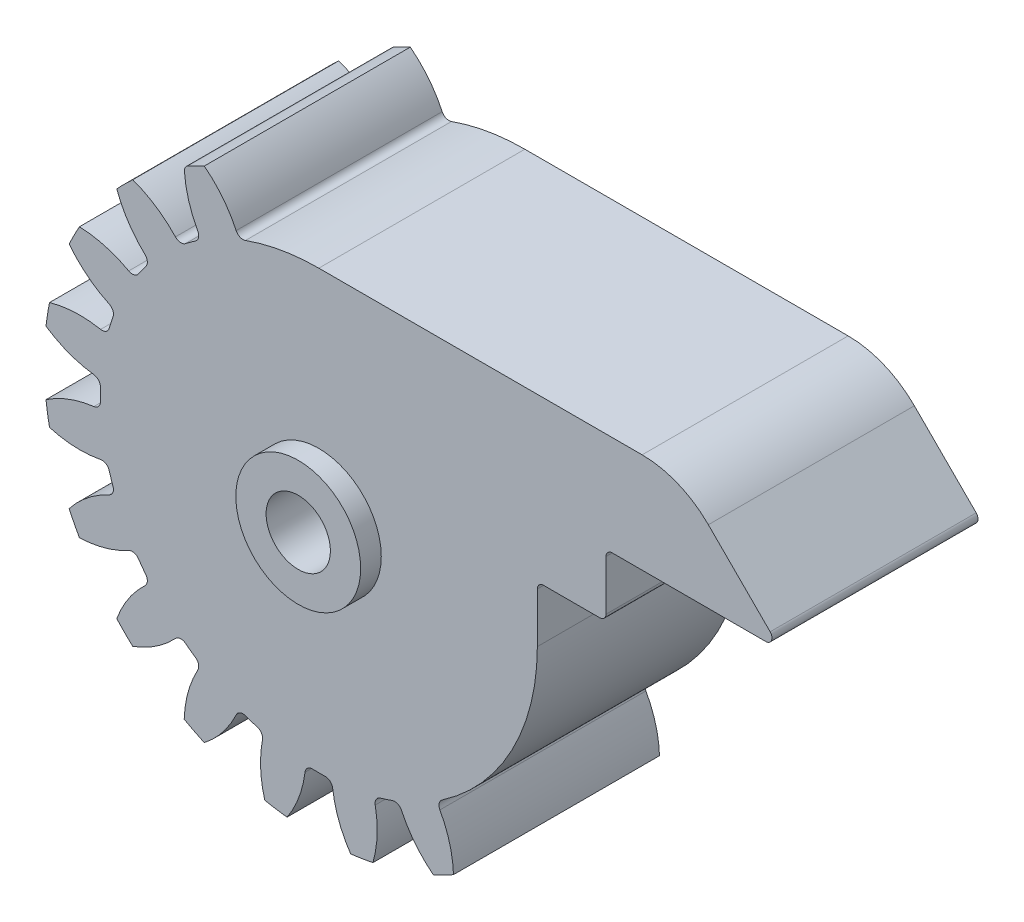
SolidWorks part; units mm, degrees
material "1023 Carbon Steel Sheet (SS)"
ref_plane "Front Plane" through (0, 0, 0) normal (0, 0, 1) x (1, 0, 0)
ref_plane "Top Plane" through (0, 0, 0) normal (0, 1, 0) x (1, 0, 0)
ref_plane "Right Plane" through (0, 0, 0) normal (1, 0, 0) x (0, 0, -1)
sketch "skBase" plane through (0, 0, 0) normal (0, 0, 1) x (1, 0, 0)
  circle A0 centre (0, 0) radius 20
  circle A1 centre (0, 0) radius 22
  circle A2 centre (0, 0) radius 17.5
  dimension "D1" = 40
  dimension "D3" = 4.5
extrude "Base" add sketch "skBase" along normal mid plane 16.5 contours A1
sketch "skToothProfile" plane through (0, 0, 0) normal (0, 0, 1) x (1, 0, 0)
  line L0 (0, 0) -> (0, 22) construction
  line L1 (-1.5692, 19.9383) -> (1.5692, 19.9383) construction
  line L2 (-1.0563, 17.4681) -> (0, 0) construction
  line L3 (0, 15.6271) -> (-2.6287, 22.8493) construction
  line L4 (0, 0) -> (3.4416, 21.7291) construction
  line L5 (1.5692, 19.9383) -> (4.6689, 19.4474) construction
  circle A0 centre (0, 0) radius 22 construction
  arc A1 (-1.0563, 17.4681) -> (-3.258, 22.7681) centre (-9.8105, 16.9387) ccw
  arc A2 (1.0563, 17.4681) -> (3.258, 22.7681) centre (9.8105, 16.9387) cw
  circle A3 centre (0, 0) radius 17.5 construction
  arc A4 (1.0563, 17.4681) -> (-1.0563, 17.4681) centre (0, 0) ccw
  circle A5 centre (0, 0) radius 20 construction
  circle A6 centre (0, 0) radius 22 construction
  circle A7 centre (0, 0) radius 23
  arc A8 (3.258, 22.7681) -> (-3.258, 22.7681) centre (0, 0) ccw
  dimension "D2" = 20
  dimension "D3" = 9
extrude "ToothProfile" cut sketch "skToothProfile" against normal through all and the other way through all
fillet "FilletToothProfile" radius 0.6 2 edges at (1.0563, 17.4681, 0) (-1.0563, 17.4681, 0)
pattern_circular "CirPatternTeeth" count 20 over 360 about axis through (0, 0, 8.25) along (0, 0, 1) of "ToothProfile", "FilletToothProfile"
sketch "skChaveta" plane through (0, 0, 8.25) normal (0, 0, 1) x (1, 0, 0)
  line L0 (0, 2.575) -> (0, 0) construction
  circle A0 centre (0, 0) radius 2.575
  dimension "D1" = 5.15
extrude "Chaveta" cut sketch "skChaveta" against normal through all contours A0
sketch "skRebaixo" plane through (0, 0, 8.25) normal (0, 0, 1) x (1, 0, 0)
  circle A0 centre (0, 0) radius 21.5
  circle A1 centre (0, 0) radius 7.5
  dimension "D1" = 43
  dimension "D2" = 15
sketch "Sketch4" plane through (0, 0, -8.25) normal (0, 0, -1) x (-1, 0, 0)
  circle A0 centre (0, 0) radius 17.5
  arc A5 (-2.5459, 21.8522) -> (-4.3314, 21.5694) centre (0, 0) ccw
  arc A6 (-2.5459, 21.8522) -> (-4.3314, 21.5694) centre (0, 0) ccw
  arc A7 (-18.0189, -1.107) -> (-21.8522, -2.5459) centre (-16.9387, -9.8105) ccw
  arc A8 (-18.0189, -1.107) -> (-21.8522, -2.5459) centre (-16.9387, -9.8105) ccw
  arc A9 (-21.5694, -4.3314) -> (-17.4791, -4.5153) centre (-19.1413, 4.096) ccw
  arc A10 (-21.5694, -4.3314) -> (-17.4791, -4.5153) centre (-19.1413, 4.096) ccw
  arc A127 (-19.996, -9.174) -> (-19.1752, -10.7848) centre (0, 0) ccw
  arc A128 (-19.996, -9.174) -> (-19.1752, -10.7848) centre (0, 0) ccw
  arc A129 (-16.1824, -14.904) -> (-14.904, -16.1824) centre (0, 0) ccw
  arc A130 (-16.1824, -14.904) -> (-14.904, -16.1824) centre (0, 0) ccw
  arc A131 (-10.7848, -19.1752) -> (-9.174, -19.996) centre (0, 0) ccw
  arc A132 (-10.7848, -19.1752) -> (-9.174, -19.996) centre (0, 0) ccw
  arc A133 (-4.3314, -21.5694) -> (-2.5459, -21.8522) centre (0, 0) ccw
  arc A134 (-4.3314, -21.5694) -> (-2.5459, -21.8522) centre (0, 0) ccw
  arc A135 (2.5459, -21.8522) -> (4.3314, -21.5694) centre (0, 0) ccw
  arc A136 (2.5459, -21.8522) -> (4.3314, -21.5694) centre (0, 0) ccw
  arc A137 (9.174, -19.996) -> (10.7848, -19.1752) centre (0, 0) ccw
  arc A138 (9.174, -19.996) -> (10.7848, -19.1752) centre (0, 0) ccw
  arc A139 (14.904, -16.1824) -> (16.1824, -14.904) centre (0, 0) ccw
  arc A140 (14.904, -16.1824) -> (16.1824, -14.904) centre (0, 0) ccw
  arc A141 (19.1752, -10.7848) -> (19.996, -9.174) centre (0, 0) ccw
  arc A142 (19.1752, -10.7848) -> (19.996, -9.174) centre (0, 0) ccw
  arc A143 (21.5694, -4.3314) -> (21.8522, -2.5459) centre (0, 0) ccw
  arc A144 (21.5694, -4.3314) -> (21.8522, -2.5459) centre (0, 0) ccw
  arc A145 (21.8522, 2.5459) -> (21.5694, 4.3314) centre (0, 0) ccw
  arc A146 (21.8522, 2.5459) -> (21.5694, 4.3314) centre (0, 0) ccw
  arc A147 (19.996, 9.174) -> (19.1752, 10.7848) centre (0, 0) ccw
  arc A148 (19.996, 9.174) -> (19.1752, 10.7848) centre (0, 0) ccw
  arc A149 (16.1824, 14.904) -> (14.904, 16.1824) centre (0, 0) ccw
  arc A150 (16.1824, 14.904) -> (14.904, 16.1824) centre (0, 0) ccw
  arc A151 (10.7848, 19.1752) -> (9.174, 19.996) centre (0, 0) ccw
  arc A152 (10.7848, 19.1752) -> (9.174, 19.996) centre (0, 0) ccw
  arc A153 (4.3314, 21.5694) -> (2.5459, 21.8522) centre (0, 0) ccw
  arc A154 (4.3314, 21.5694) -> (2.5459, 21.8522) centre (0, 0) ccw
  arc A155 (-9.174, 19.996) -> (-10.7848, 19.1752) centre (0, 0) ccw
  arc A156 (-9.174, 19.996) -> (-10.7848, 19.1752) centre (0, 0) ccw
  arc A157 (-14.904, 16.1824) -> (-16.1824, 14.904) centre (0, 0) ccw
  arc A158 (-14.904, 16.1824) -> (-16.1824, 14.904) centre (0, 0) ccw
  arc A159 (-19.1752, 10.7848) -> (-19.996, 9.174) centre (0, 0) ccw
  arc A160 (-19.1752, 10.7848) -> (-19.996, 9.174) centre (0, 0) ccw
  arc A161 (-21.5694, 4.3314) -> (-21.8522, 2.5459) centre (0, 0) ccw
  arc A162 (-21.5694, 4.3314) -> (-21.8522, 2.5459) centre (0, 0) ccw
  arc A163 (-4.3314, 21.5694) -> (-4.5153, 17.4791) centre (4.096, 19.1413) ccw
  arc A164 (-4.3314, 21.5694) -> (-4.5153, 17.4791) centre (4.096, 19.1413) ccw
  arc A165 (-4.9352, 16.7897) -> (-4.5153, 17.4791) centre (-5.1044, 17.3653) ccw
  arc A166 (-4.9352, 16.7897) -> (-4.5153, 17.4791) centre (-5.1044, 17.3653) ccw
  arc A167 (-4.9352, 16.7897) -> (-5.8761, 16.484) centre (0, 0) ccw
  arc A168 (-4.9352, 16.7897) -> (-5.8761, 16.484) centre (0, 0) ccw
  arc A169 (-6.621, 16.7949) -> (-5.8761, 16.484) centre (-6.0775, 17.0492) ccw
  arc A170 (-6.621, 16.7949) -> (-5.8761, 16.484) centre (-6.0775, 17.0492) ccw
  arc A171 (-6.621, 16.7949) -> (-9.174, 19.996) centre (-14.5647, 13.0781) ccw
  arc A172 (-6.621, 16.7949) -> (-9.174, 19.996) centre (-14.5647, 13.0781) ccw
  arc A173 (-10.7848, 19.1752) -> (-9.6956, 15.2283) centre (-2.0195, 19.4702) ccw
  arc A174 (-10.7848, 19.1752) -> (-9.6956, 15.2283) centre (-2.0195, 19.4702) ccw
  arc A175 (-9.882, 14.4429) -> (-9.6956, 15.2283) centre (-10.2208, 14.9381) ccw
  arc A176 (-9.882, 14.4429) -> (-9.6956, 15.2283) centre (-10.2208, 14.9381) ccw
  arc A177 (-9.882, 14.4429) -> (-10.6823, 13.8614) centre (0, 0) ccw
  arc A178 (-9.882, 14.4429) -> (-10.6823, 13.8614) centre (0, 0) ccw
  arc A179 (-11.4868, 13.9269) -> (-10.6823, 13.8614) centre (-11.0486, 14.3366) ccw
  arc A180 (-11.4868, 13.9269) -> (-10.6823, 13.8614) centre (-11.0486, 14.3366) ccw
  arc A181 (-11.4868, 13.9269) -> (-14.904, 16.1824) centre (-17.8932, 7.9372) ccw
  arc A182 (-11.4868, 13.9269) -> (-14.904, 16.1824) centre (-17.8932, 7.9372) ccw
  arc A183 (-16.1824, 14.904) -> (-13.9269, 11.4868) centre (-7.9372, 17.8932) ccw
  arc A184 (-16.1824, 14.904) -> (-13.9269, 11.4868) centre (-7.9372, 17.8932) ccw
  arc A185 (-13.8614, 10.6823) -> (-13.9269, 11.4868) centre (-14.3366, 11.0486) ccw
  arc A186 (-13.8614, 10.6823) -> (-13.9269, 11.4868) centre (-14.3366, 11.0486) ccw
  arc A187 (-13.8614, 10.6823) -> (-14.4429, 9.882) centre (0, 0) ccw
  arc A188 (-13.8614, 10.6823) -> (-14.4429, 9.882) centre (0, 0) ccw
  arc A189 (-15.2283, 9.6956) -> (-14.4429, 9.882) centre (-14.9381, 10.2208) ccw
  arc A190 (-15.2283, 9.6956) -> (-14.4429, 9.882) centre (-14.9381, 10.2208) ccw
  arc A191 (-15.2283, 9.6956) -> (-19.1752, 10.7848) centre (-19.4702, 2.0195) ccw
  arc A192 (-15.2283, 9.6956) -> (-19.1752, 10.7848) centre (-19.4702, 2.0195) ccw
  arc A193 (-19.996, 9.174) -> (-16.7949, 6.621) centre (-13.0781, 14.5647) ccw
  arc A194 (-19.996, 9.174) -> (-16.7949, 6.621) centre (-13.0781, 14.5647) ccw
  arc A195 (-16.484, 5.8761) -> (-16.7949, 6.621) centre (-17.0492, 6.0775) ccw
  arc A196 (-16.484, 5.8761) -> (-16.7949, 6.621) centre (-17.0492, 6.0775) ccw
  arc A197 (-16.484, 5.8761) -> (-16.7897, 4.9352) centre (0, 0) ccw
  arc A198 (-16.484, 5.8761) -> (-16.7897, 4.9352) centre (0, 0) ccw
  arc A199 (-17.4791, 4.5153) -> (-16.7897, 4.9352) centre (-17.3653, 5.1044) ccw
  arc A200 (-17.4791, 4.5153) -> (-16.7897, 4.9352) centre (-17.3653, 5.1044) ccw
  arc A201 (-17.4791, 4.5153) -> (-21.5694, 4.3314) centre (-19.1413, -4.096) ccw
  arc A202 (-17.4791, 4.5153) -> (-21.5694, 4.3314) centre (-19.1413, -4.096) ccw
  arc A203 (-21.8522, 2.5459) -> (-18.0189, 1.107) centre (-16.9387, 9.8105) ccw
  arc A204 (-21.8522, 2.5459) -> (-18.0189, 1.107) centre (-16.9387, 9.8105) ccw
  arc A205 (-17.493, 0.4946) -> (-18.0189, 1.107) centre (-18.0928, 0.5116) ccw
  arc A206 (-17.493, 0.4946) -> (-18.0189, 1.107) centre (-18.0928, 0.5116) ccw
  arc A207 (-17.493, 0.4946) -> (-17.493, -0.4946) centre (0, 0) ccw
  arc A208 (-17.493, 0.4946) -> (-17.493, -0.4946) centre (0, 0) ccw
  arc A209 (-18.0189, -1.107) -> (-17.493, -0.4946) centre (-18.0928, -0.5116) ccw
  arc A210 (-18.0189, -1.107) -> (-17.493, -0.4946) centre (-18.0928, -0.5116) ccw
  arc A211 (-16.7897, -4.9352) -> (-17.4791, -4.5153) centre (-17.3653, -5.1044) ccw
  arc A212 (-16.7897, -4.9352) -> (-17.4791, -4.5153) centre (-17.3653, -5.1044) ccw
  arc A213 (-16.7897, -4.9352) -> (-16.484, -5.8761) centre (0, 0) ccw
  arc A214 (-16.7897, -4.9352) -> (-16.484, -5.8761) centre (0, 0) ccw
  arc A215 (-16.7949, -6.621) -> (-16.484, -5.8761) centre (-17.0492, -6.0775) ccw
  arc A216 (-16.7949, -6.621) -> (-16.484, -5.8761) centre (-17.0492, -6.0775) ccw
  arc A217 (-16.7949, -6.621) -> (-19.996, -9.174) centre (-13.0781, -14.5647) ccw
  arc A218 (-16.7949, -6.621) -> (-19.996, -9.174) centre (-13.0781, -14.5647) ccw
  arc A219 (-19.1752, -10.7848) -> (-15.2283, -9.6956) centre (-19.4702, -2.0195) ccw
  arc A220 (-19.1752, -10.7848) -> (-15.2283, -9.6956) centre (-19.4702, -2.0195) ccw
  arc A221 (-14.4429, -9.882) -> (-15.2283, -9.6956) centre (-14.9381, -10.2208) ccw
  arc A222 (-14.4429, -9.882) -> (-15.2283, -9.6956) centre (-14.9381, -10.2208) ccw
  arc A223 (-14.4429, -9.882) -> (-13.8614, -10.6823) centre (0, 0) ccw
  arc A224 (-14.4429, -9.882) -> (-13.8614, -10.6823) centre (0, 0) ccw
  arc A225 (-13.9269, -11.4868) -> (-13.8614, -10.6823) centre (-14.3366, -11.0486) ccw
  arc A226 (-13.9269, -11.4868) -> (-13.8614, -10.6823) centre (-14.3366, -11.0486) ccw
  arc A227 (-13.9269, -11.4868) -> (-16.1824, -14.904) centre (-7.9372, -17.8932) ccw
  arc A228 (-13.9269, -11.4868) -> (-16.1824, -14.904) centre (-7.9372, -17.8932) ccw
  arc A229 (-14.904, -16.1824) -> (-11.4868, -13.9269) centre (-17.8932, -7.9372) ccw
  arc A230 (-14.904, -16.1824) -> (-11.4868, -13.9269) centre (-17.8932, -7.9372) ccw
  arc A231 (-10.6823, -13.8614) -> (-11.4868, -13.9269) centre (-11.0486, -14.3366) ccw
  arc A232 (-10.6823, -13.8614) -> (-11.4868, -13.9269) centre (-11.0486, -14.3366) ccw
  arc A233 (-10.6823, -13.8614) -> (-9.882, -14.4429) centre (0, 0) ccw
  arc A234 (-10.6823, -13.8614) -> (-9.882, -14.4429) centre (0, 0) ccw
  arc A235 (-9.6956, -15.2283) -> (-9.882, -14.4429) centre (-10.2208, -14.9381) ccw
  arc A236 (-9.6956, -15.2283) -> (-9.882, -14.4429) centre (-10.2208, -14.9381) ccw
  arc A237 (-9.6956, -15.2283) -> (-10.7848, -19.1752) centre (-2.0195, -19.4702) ccw
  arc A238 (-9.6956, -15.2283) -> (-10.7848, -19.1752) centre (-2.0195, -19.4702) ccw
  arc A239 (-9.174, -19.996) -> (-6.621, -16.7949) centre (-14.5647, -13.0781) ccw
  arc A240 (-9.174, -19.996) -> (-6.621, -16.7949) centre (-14.5647, -13.0781) ccw
  arc A241 (-5.8761, -16.484) -> (-6.621, -16.7949) centre (-6.0775, -17.0492) ccw
  arc A242 (-5.8761, -16.484) -> (-6.621, -16.7949) centre (-6.0775, -17.0492) ccw
  arc A243 (-5.8761, -16.484) -> (-4.9352, -16.7897) centre (0, 0) ccw
  arc A244 (-5.8761, -16.484) -> (-4.9352, -16.7897) centre (0, 0) ccw
  arc A245 (-4.5153, -17.4791) -> (-4.9352, -16.7897) centre (-5.1044, -17.3653) ccw
  arc A246 (-4.5153, -17.4791) -> (-4.9352, -16.7897) centre (-5.1044, -17.3653) ccw
  arc A247 (-4.5153, -17.4791) -> (-4.3314, -21.5694) centre (4.096, -19.1413) ccw
  arc A248 (-4.5153, -17.4791) -> (-4.3314, -21.5694) centre (4.096, -19.1413) ccw
  arc A249 (-2.5459, -21.8522) -> (-1.107, -18.0189) centre (-9.8105, -16.9387) ccw
  arc A250 (-2.5459, -21.8522) -> (-1.107, -18.0189) centre (-9.8105, -16.9387) ccw
  arc A251 (-0.4946, -17.493) -> (-1.107, -18.0189) centre (-0.5116, -18.0928) ccw
  arc A252 (-0.4946, -17.493) -> (-1.107, -18.0189) centre (-0.5116, -18.0928) ccw
  arc A253 (-0.4946, -17.493) -> (0.4946, -17.493) centre (0, 0) ccw
  arc A254 (-0.4946, -17.493) -> (0.4946, -17.493) centre (0, 0) ccw
  arc A255 (1.107, -18.0189) -> (0.4946, -17.493) centre (0.5116, -18.0928) ccw
  arc A256 (1.107, -18.0189) -> (0.4946, -17.493) centre (0.5116, -18.0928) ccw
  arc A257 (1.107, -18.0189) -> (2.5459, -21.8522) centre (9.8105, -16.9387) ccw
  arc A258 (1.107, -18.0189) -> (2.5459, -21.8522) centre (9.8105, -16.9387) ccw
  arc A259 (4.3314, -21.5694) -> (4.5153, -17.4791) centre (-4.096, -19.1413) ccw
  arc A260 (4.3314, -21.5694) -> (4.5153, -17.4791) centre (-4.096, -19.1413) ccw
  arc A261 (4.9352, -16.7897) -> (4.5153, -17.4791) centre (5.1044, -17.3653) ccw
  arc A262 (4.9352, -16.7897) -> (4.5153, -17.4791) centre (5.1044, -17.3653) ccw
  arc A263 (4.9352, -16.7897) -> (5.8761, -16.484) centre (0, 0) ccw
  arc A264 (4.9352, -16.7897) -> (5.8761, -16.484) centre (0, 0) ccw
  arc A265 (6.621, -16.7949) -> (5.8761, -16.484) centre (6.0775, -17.0492) ccw
  arc A266 (6.621, -16.7949) -> (5.8761, -16.484) centre (6.0775, -17.0492) ccw
  arc A267 (6.621, -16.7949) -> (9.174, -19.996) centre (14.5647, -13.0781) ccw
  arc A268 (6.621, -16.7949) -> (9.174, -19.996) centre (14.5647, -13.0781) ccw
  arc A269 (10.7848, -19.1752) -> (9.6956, -15.2283) centre (2.0195, -19.4702) ccw
  arc A270 (10.7848, -19.1752) -> (9.6956, -15.2283) centre (2.0195, -19.4702) ccw
  arc A271 (9.882, -14.4429) -> (9.6956, -15.2283) centre (10.2208, -14.9381) ccw
  arc A272 (9.882, -14.4429) -> (9.6956, -15.2283) centre (10.2208, -14.9381) ccw
  arc A273 (9.882, -14.4429) -> (10.6823, -13.8614) centre (0, 0) ccw
  arc A274 (9.882, -14.4429) -> (10.6823, -13.8614) centre (0, 0) ccw
  arc A275 (11.4868, -13.9269) -> (10.6823, -13.8614) centre (11.0486, -14.3366) ccw
  arc A276 (11.4868, -13.9269) -> (10.6823, -13.8614) centre (11.0486, -14.3366) ccw
  arc A277 (11.4868, -13.9269) -> (14.904, -16.1824) centre (17.8932, -7.9372) ccw
  arc A278 (11.4868, -13.9269) -> (14.904, -16.1824) centre (17.8932, -7.9372) ccw
  arc A279 (16.1824, -14.904) -> (13.9269, -11.4868) centre (7.9372, -17.8932) ccw
  arc A280 (16.1824, -14.904) -> (13.9269, -11.4868) centre (7.9372, -17.8932) ccw
  arc A281 (13.8614, -10.6823) -> (13.9269, -11.4868) centre (14.3366, -11.0486) ccw
  arc A282 (13.8614, -10.6823) -> (13.9269, -11.4868) centre (14.3366, -11.0486) ccw
  arc A283 (13.8614, -10.6823) -> (14.4429, -9.882) centre (0, 0) ccw
  arc A284 (13.8614, -10.6823) -> (14.4429, -9.882) centre (0, 0) ccw
  arc A285 (15.2283, -9.6956) -> (14.4429, -9.882) centre (14.9381, -10.2208) ccw
  arc A286 (15.2283, -9.6956) -> (14.4429, -9.882) centre (14.9381, -10.2208) ccw
  arc A287 (15.2283, -9.6956) -> (19.1752, -10.7848) centre (19.4702, -2.0195) ccw
  arc A288 (15.2283, -9.6956) -> (19.1752, -10.7848) centre (19.4702, -2.0195) ccw
  arc A289 (19.996, -9.174) -> (16.7949, -6.621) centre (13.0781, -14.5647) ccw
  arc A290 (19.996, -9.174) -> (16.7949, -6.621) centre (13.0781, -14.5647) ccw
  arc A291 (16.484, -5.8761) -> (16.7949, -6.621) centre (17.0492, -6.0775) ccw
  arc A292 (16.484, -5.8761) -> (16.7949, -6.621) centre (17.0492, -6.0775) ccw
  arc A293 (16.484, -5.8761) -> (16.7897, -4.9352) centre (0, 0) ccw
  arc A294 (16.484, -5.8761) -> (16.7897, -4.9352) centre (0, 0) ccw
  arc A295 (17.4791, -4.5153) -> (16.7897, -4.9352) centre (17.3653, -5.1044) ccw
  arc A296 (17.4791, -4.5153) -> (16.7897, -4.9352) centre (17.3653, -5.1044) ccw
  arc A297 (17.4791, -4.5153) -> (21.5694, -4.3314) centre (19.1413, 4.096) ccw
  arc A298 (17.4791, -4.5153) -> (21.5694, -4.3314) centre (19.1413, 4.096) ccw
  arc A299 (21.8522, -2.5459) -> (18.0189, -1.107) centre (16.9387, -9.8105) ccw
  arc A300 (21.8522, -2.5459) -> (18.0189, -1.107) centre (16.9387, -9.8105) ccw
  arc A301 (17.493, -0.4946) -> (18.0189, -1.107) centre (18.0928, -0.5116) ccw
  arc A302 (17.493, -0.4946) -> (18.0189, -1.107) centre (18.0928, -0.5116) ccw
  arc A303 (17.493, -0.4946) -> (17.493, 0.4946) centre (0, 0) ccw
  arc A304 (17.493, -0.4946) -> (17.493, 0.4946) centre (0, 0) ccw
  arc A305 (18.0189, 1.107) -> (17.493, 0.4946) centre (18.0928, 0.5116) ccw
  arc A306 (18.0189, 1.107) -> (17.493, 0.4946) centre (18.0928, 0.5116) ccw
  arc A307 (18.0189, 1.107) -> (21.8522, 2.5459) centre (16.9387, 9.8105) ccw
  arc A308 (18.0189, 1.107) -> (21.8522, 2.5459) centre (16.9387, 9.8105) ccw
  arc A309 (21.5694, 4.3314) -> (17.4791, 4.5153) centre (19.1413, -4.096) ccw
  arc A310 (21.5694, 4.3314) -> (17.4791, 4.5153) centre (19.1413, -4.096) ccw
  arc A311 (-21.8522, -2.5459) -> (-21.5694, -4.3314) centre (0, 0) ccw
  arc A312 (-21.8522, -2.5459) -> (-21.5694, -4.3314) centre (0, 0) ccw
  arc A313 (16.7897, 4.9352) -> (17.4791, 4.5153) centre (17.3653, 5.1044) ccw
  arc A314 (16.7897, 4.9352) -> (17.4791, 4.5153) centre (17.3653, 5.1044) ccw
  arc A315 (16.7897, 4.9352) -> (16.484, 5.8761) centre (0, 0) ccw
  arc A316 (16.7897, 4.9352) -> (16.484, 5.8761) centre (0, 0) ccw
  arc A317 (16.7949, 6.621) -> (16.484, 5.8761) centre (17.0492, 6.0775) ccw
  arc A318 (16.7949, 6.621) -> (16.484, 5.8761) centre (17.0492, 6.0775) ccw
  arc A319 (16.7949, 6.621) -> (19.996, 9.174) centre (13.0781, 14.5647) ccw
  arc A320 (16.7949, 6.621) -> (19.996, 9.174) centre (13.0781, 14.5647) ccw
  arc A321 (19.1752, 10.7848) -> (15.2283, 9.6956) centre (19.4702, 2.0195) ccw
  arc A322 (19.1752, 10.7848) -> (15.2283, 9.6956) centre (19.4702, 2.0195) ccw
  arc A323 (14.4429, 9.882) -> (15.2283, 9.6956) centre (14.9381, 10.2208) ccw
  arc A324 (14.4429, 9.882) -> (15.2283, 9.6956) centre (14.9381, 10.2208) ccw
  arc A325 (14.4429, 9.882) -> (13.8614, 10.6823) centre (0, 0) ccw
  arc A326 (14.4429, 9.882) -> (13.8614, 10.6823) centre (0, 0) ccw
  arc A327 (13.9269, 11.4868) -> (13.8614, 10.6823) centre (14.3366, 11.0486) ccw
  arc A328 (13.9269, 11.4868) -> (13.8614, 10.6823) centre (14.3366, 11.0486) ccw
  arc A329 (13.9269, 11.4868) -> (16.1824, 14.904) centre (7.9372, 17.8932) ccw
  arc A330 (13.9269, 11.4868) -> (16.1824, 14.904) centre (7.9372, 17.8932) ccw
  arc A331 (14.904, 16.1824) -> (11.4868, 13.9269) centre (17.8932, 7.9372) ccw
  arc A332 (14.904, 16.1824) -> (11.4868, 13.9269) centre (17.8932, 7.9372) ccw
  arc A333 (10.6823, 13.8614) -> (11.4868, 13.9269) centre (11.0486, 14.3366) ccw
  arc A334 (10.6823, 13.8614) -> (11.4868, 13.9269) centre (11.0486, 14.3366) ccw
  arc A335 (10.6823, 13.8614) -> (9.882, 14.4429) centre (0, 0) ccw
  arc A336 (10.6823, 13.8614) -> (9.882, 14.4429) centre (0, 0) ccw
  arc A337 (9.6956, 15.2283) -> (9.882, 14.4429) centre (10.2208, 14.9381) ccw
  arc A338 (9.6956, 15.2283) -> (9.882, 14.4429) centre (10.2208, 14.9381) ccw
  arc A339 (9.6956, 15.2283) -> (10.7848, 19.1752) centre (2.0195, 19.4702) ccw
  arc A340 (9.6956, 15.2283) -> (10.7848, 19.1752) centre (2.0195, 19.4702) ccw
  arc A341 (9.174, 19.996) -> (6.621, 16.7949) centre (14.5647, 13.0781) ccw
  arc A342 (9.174, 19.996) -> (6.621, 16.7949) centre (14.5647, 13.0781) ccw
  arc A343 (5.8761, 16.484) -> (6.621, 16.7949) centre (6.0775, 17.0492) ccw
  arc A344 (5.8761, 16.484) -> (6.621, 16.7949) centre (6.0775, 17.0492) ccw
  arc A345 (5.8761, 16.484) -> (4.9352, 16.7897) centre (0, 0) ccw
  arc A346 (5.8761, 16.484) -> (4.9352, 16.7897) centre (0, 0) ccw
  arc A347 (4.5153, 17.4791) -> (4.9352, 16.7897) centre (5.1044, 17.3653) ccw
  arc A348 (4.5153, 17.4791) -> (4.9352, 16.7897) centre (5.1044, 17.3653) ccw
  arc A349 (4.5153, 17.4791) -> (4.3314, 21.5694) centre (-4.096, 19.1413) ccw
  arc A350 (4.5153, 17.4791) -> (4.3314, 21.5694) centre (-4.096, 19.1413) ccw
  arc A351 (2.5459, 21.8522) -> (1.107, 18.0189) centre (9.8105, 16.9387) ccw
  arc A352 (2.5459, 21.8522) -> (1.107, 18.0189) centre (9.8105, 16.9387) ccw
  arc A353 (0.4946, 17.493) -> (1.107, 18.0189) centre (0.5116, 18.0928) ccw
  arc A354 (0.4946, 17.493) -> (1.107, 18.0189) centre (0.5116, 18.0928) ccw
  arc A355 (0.4946, 17.493) -> (-0.4946, 17.493) centre (0, 0) ccw
  arc A356 (0.4946, 17.493) -> (-0.4946, 17.493) centre (0, 0) ccw
  arc A357 (-1.107, 18.0189) -> (-0.4946, 17.493) centre (-0.5116, 18.0928) ccw
  arc A358 (-1.107, 18.0189) -> (-0.4946, 17.493) centre (-0.5116, 18.0928) ccw
  arc A359 (-1.107, 18.0189) -> (-2.5459, 21.8522) centre (-9.8105, 16.9387) ccw
  arc A360 (-1.107, 18.0189) -> (-2.5459, 21.8522) centre (-9.8105, 16.9387) ccw
  dimension "D1" = 0
sketch "Sketch6" plane through (0, 0, -8.25) normal (0, 0, -1) x (-1, 0, 0)
  circle A0 centre (0, 0) radius 20 construction
  dimension "D1" = 40
sketch "Sketch7" plane through (0, 0, -8.25) normal (0, 0, -1) x (-1, 0, 0)
  circle A0 centre (0, 0) radius 17.5
  arc A120 (-2.5459, 21.8522) -> (-4.3314, 21.5694) centre (0, 0) ccw
  arc A121 (-4.3314, 21.5694) -> (-4.5153, 17.4791) centre (4.096, 19.1413) ccw
  arc A122 (-4.9352, 16.7897) -> (-4.5153, 17.4791) centre (-5.1044, 17.3653) ccw
  arc A123 (-4.9352, 16.7897) -> (-5.8761, 16.484) centre (0, 0) ccw
  arc A124 (-6.621, 16.7949) -> (-5.8761, 16.484) centre (-6.0775, 17.0492) ccw
  arc A125 (-6.621, 16.7949) -> (-9.174, 19.996) centre (-14.5647, 13.0781) ccw
  arc A126 (-9.174, 19.996) -> (-10.7848, 19.1752) centre (0, 0) ccw
  arc A127 (-10.7848, 19.1752) -> (-9.6956, 15.2283) centre (-2.0195, 19.4702) ccw
  arc A128 (-9.882, 14.4429) -> (-9.6956, 15.2283) centre (-10.2208, 14.9381) ccw
  arc A129 (-9.882, 14.4429) -> (-10.6823, 13.8614) centre (0, 0) ccw
  arc A130 (-11.4868, 13.9269) -> (-10.6823, 13.8614) centre (-11.0486, 14.3366) ccw
  arc A131 (-11.4868, 13.9269) -> (-14.904, 16.1824) centre (-17.8932, 7.9372) ccw
  arc A132 (-14.904, 16.1824) -> (-16.1824, 14.904) centre (0, 0) ccw
  arc A133 (-16.1824, 14.904) -> (-13.9269, 11.4868) centre (-7.9372, 17.8932) ccw
  arc A134 (-13.8614, 10.6823) -> (-13.9269, 11.4868) centre (-14.3366, 11.0486) ccw
  arc A135 (-13.8614, 10.6823) -> (-14.4429, 9.882) centre (0, 0) ccw
  arc A136 (-15.2283, 9.6956) -> (-14.4429, 9.882) centre (-14.9381, 10.2208) ccw
  arc A137 (-15.2283, 9.6956) -> (-19.1752, 10.7848) centre (-19.4702, 2.0195) ccw
  arc A138 (-19.1752, 10.7848) -> (-19.996, 9.174) centre (0, 0) ccw
  arc A139 (-19.996, 9.174) -> (-16.7949, 6.621) centre (-13.0781, 14.5647) ccw
  arc A140 (-16.484, 5.8761) -> (-16.7949, 6.621) centre (-17.0492, 6.0775) ccw
  arc A141 (-16.484, 5.8761) -> (-16.7897, 4.9352) centre (0, 0) ccw
  arc A142 (-17.4791, 4.5153) -> (-16.7897, 4.9352) centre (-17.3653, 5.1044) ccw
  arc A143 (-17.4791, 4.5153) -> (-21.5694, 4.3314) centre (-19.1413, -4.096) ccw
  arc A144 (-21.5694, 4.3314) -> (-21.8522, 2.5459) centre (0, 0) ccw
  arc A145 (-21.8522, 2.5459) -> (-18.0189, 1.107) centre (-16.9387, 9.8105) ccw
  arc A146 (-17.493, 0.4946) -> (-18.0189, 1.107) centre (-18.0928, 0.5116) ccw
  arc A147 (-17.493, 0.4946) -> (-17.493, -0.4946) centre (0, 0) ccw
  arc A148 (-18.0189, -1.107) -> (-17.493, -0.4946) centre (-18.0928, -0.5116) ccw
  arc A149 (-18.0189, -1.107) -> (-21.8522, -2.5459) centre (-16.9387, -9.8105) ccw
  arc A150 (-21.8522, -2.5459) -> (-21.5694, -4.3314) centre (0, 0) ccw
  arc A151 (-21.5694, -4.3314) -> (-17.4791, -4.5153) centre (-19.1413, 4.096) ccw
  arc A152 (-16.7897, -4.9352) -> (-17.4791, -4.5153) centre (-17.3653, -5.1044) ccw
  arc A153 (-16.7897, -4.9352) -> (-16.484, -5.8761) centre (0, 0) ccw
  arc A154 (-16.7949, -6.621) -> (-16.484, -5.8761) centre (-17.0492, -6.0775) ccw
  arc A155 (-16.7949, -6.621) -> (-19.996, -9.174) centre (-13.0781, -14.5647) ccw
  arc A156 (-19.996, -9.174) -> (-19.1752, -10.7848) centre (0, 0) ccw
  arc A157 (-19.1752, -10.7848) -> (-15.2283, -9.6956) centre (-19.4702, -2.0195) ccw
  arc A158 (-14.4429, -9.882) -> (-15.2283, -9.6956) centre (-14.9381, -10.2208) ccw
  arc A159 (-14.4429, -9.882) -> (-13.8614, -10.6823) centre (0, 0) ccw
  arc A160 (-13.9269, -11.4868) -> (-13.8614, -10.6823) centre (-14.3366, -11.0486) ccw
  arc A161 (-13.9269, -11.4868) -> (-16.1824, -14.904) centre (-7.9372, -17.8932) ccw
  arc A162 (-16.1824, -14.904) -> (-14.904, -16.1824) centre (0, 0) ccw
  arc A163 (-14.904, -16.1824) -> (-11.4868, -13.9269) centre (-17.8932, -7.9372) ccw
  arc A164 (-10.6823, -13.8614) -> (-11.4868, -13.9269) centre (-11.0486, -14.3366) ccw
  arc A165 (-10.6823, -13.8614) -> (-9.882, -14.4429) centre (0, 0) ccw
  arc A166 (-9.6956, -15.2283) -> (-9.882, -14.4429) centre (-10.2208, -14.9381) ccw
  arc A167 (-9.6956, -15.2283) -> (-10.7848, -19.1752) centre (-2.0195, -19.4702) ccw
  arc A168 (-10.7848, -19.1752) -> (-9.174, -19.996) centre (0, 0) ccw
  arc A169 (-9.174, -19.996) -> (-6.621, -16.7949) centre (-14.5647, -13.0781) ccw
  arc A170 (-5.8761, -16.484) -> (-6.621, -16.7949) centre (-6.0775, -17.0492) ccw
  arc A171 (-5.8761, -16.484) -> (-4.9352, -16.7897) centre (0, 0) ccw
  arc A172 (-4.5153, -17.4791) -> (-4.9352, -16.7897) centre (-5.1044, -17.3653) ccw
  arc A173 (-4.5153, -17.4791) -> (-4.3314, -21.5694) centre (4.096, -19.1413) ccw
  arc A174 (-4.3314, -21.5694) -> (-2.5459, -21.8522) centre (0, 0) ccw
  arc A175 (-2.5459, -21.8522) -> (-1.107, -18.0189) centre (-9.8105, -16.9387) ccw
  arc A176 (-0.4946, -17.493) -> (-1.107, -18.0189) centre (-0.5116, -18.0928) ccw
  arc A177 (-0.4946, -17.493) -> (0.4946, -17.493) centre (0, 0) ccw
  arc A178 (1.107, -18.0189) -> (0.4946, -17.493) centre (0.5116, -18.0928) ccw
  arc A179 (1.107, -18.0189) -> (2.5459, -21.8522) centre (9.8105, -16.9387) ccw
  arc A180 (2.5459, -21.8522) -> (4.3314, -21.5694) centre (0, 0) ccw
  arc A181 (4.3314, -21.5694) -> (4.5153, -17.4791) centre (-4.096, -19.1413) ccw
  arc A182 (4.9352, -16.7897) -> (4.5153, -17.4791) centre (5.1044, -17.3653) ccw
  arc A183 (4.9352, -16.7897) -> (5.8761, -16.484) centre (0, 0) ccw
  arc A184 (6.621, -16.7949) -> (5.8761, -16.484) centre (6.0775, -17.0492) ccw
  arc A185 (6.621, -16.7949) -> (9.174, -19.996) centre (14.5647, -13.0781) ccw
  arc A186 (9.174, -19.996) -> (10.7848, -19.1752) centre (0, 0) ccw
  arc A187 (10.7848, -19.1752) -> (9.6956, -15.2283) centre (2.0195, -19.4702) ccw
  arc A188 (9.882, -14.4429) -> (9.6956, -15.2283) centre (10.2208, -14.9381) ccw
  arc A189 (9.882, -14.4429) -> (10.6823, -13.8614) centre (0, 0) ccw
  arc A190 (11.4868, -13.9269) -> (10.6823, -13.8614) centre (11.0486, -14.3366) ccw
  arc A191 (11.4868, -13.9269) -> (14.904, -16.1824) centre (17.8932, -7.9372) ccw
  arc A192 (14.904, -16.1824) -> (16.1824, -14.904) centre (0, 0) ccw
  arc A193 (16.1824, -14.904) -> (13.9269, -11.4868) centre (7.9372, -17.8932) ccw
  arc A194 (13.8614, -10.6823) -> (13.9269, -11.4868) centre (14.3366, -11.0486) ccw
  arc A195 (13.8614, -10.6823) -> (14.4429, -9.882) centre (0, 0) ccw
  arc A196 (15.2283, -9.6956) -> (14.4429, -9.882) centre (14.9381, -10.2208) ccw
  arc A197 (15.2283, -9.6956) -> (19.1752, -10.7848) centre (19.4702, -2.0195) ccw
  arc A198 (19.1752, -10.7848) -> (19.996, -9.174) centre (0, 0) ccw
  arc A199 (19.996, -9.174) -> (16.7949, -6.621) centre (13.0781, -14.5647) ccw
  arc A200 (16.484, -5.8761) -> (16.7949, -6.621) centre (17.0492, -6.0775) ccw
  arc A201 (16.484, -5.8761) -> (16.7897, -4.9352) centre (0, 0) ccw
  arc A202 (17.4791, -4.5153) -> (16.7897, -4.9352) centre (17.3653, -5.1044) ccw
  arc A203 (17.4791, -4.5153) -> (21.5694, -4.3314) centre (19.1413, 4.096) ccw
  arc A204 (21.5694, -4.3314) -> (21.8522, -2.5459) centre (0, 0) ccw
  arc A205 (21.8522, -2.5459) -> (18.0189, -1.107) centre (16.9387, -9.8105) ccw
  arc A206 (17.493, -0.4946) -> (18.0189, -1.107) centre (18.0928, -0.5116) ccw
  arc A207 (17.493, -0.4946) -> (17.493, 0.4946) centre (0, 0) ccw
  arc A208 (18.0189, 1.107) -> (17.493, 0.4946) centre (18.0928, 0.5116) ccw
  arc A209 (18.0189, 1.107) -> (21.8522, 2.5459) centre (16.9387, 9.8105) ccw
  arc A210 (21.8522, 2.5459) -> (21.5694, 4.3314) centre (0, 0) ccw
  arc A211 (21.5694, 4.3314) -> (17.4791, 4.5153) centre (19.1413, -4.096) ccw
  arc A212 (16.7897, 4.9352) -> (17.4791, 4.5153) centre (17.3653, 5.1044) ccw
  arc A213 (16.7897, 4.9352) -> (16.484, 5.8761) centre (0, 0) ccw
  arc A214 (16.7949, 6.621) -> (16.484, 5.8761) centre (17.0492, 6.0775) ccw
  arc A215 (16.7949, 6.621) -> (19.996, 9.174) centre (13.0781, 14.5647) ccw
  arc A216 (19.996, 9.174) -> (19.1752, 10.7848) centre (0, 0) ccw
  arc A217 (19.1752, 10.7848) -> (15.2283, 9.6956) centre (19.4702, 2.0195) ccw
  arc A218 (14.4429, 9.882) -> (15.2283, 9.6956) centre (14.9381, 10.2208) ccw
  arc A219 (14.4429, 9.882) -> (13.8614, 10.6823) centre (0, 0) ccw
  arc A220 (13.9269, 11.4868) -> (13.8614, 10.6823) centre (14.3366, 11.0486) ccw
  arc A221 (13.9269, 11.4868) -> (16.1824, 14.904) centre (7.9372, 17.8932) ccw
  arc A222 (16.1824, 14.904) -> (14.904, 16.1824) centre (0, 0) ccw
  arc A223 (14.904, 16.1824) -> (11.4868, 13.9269) centre (17.8932, 7.9372) ccw
  arc A224 (10.6823, 13.8614) -> (11.4868, 13.9269) centre (11.0486, 14.3366) ccw
  arc A225 (10.6823, 13.8614) -> (9.882, 14.4429) centre (0, 0) ccw
  arc A226 (9.6956, 15.2283) -> (9.882, 14.4429) centre (10.2208, 14.9381) ccw
  arc A227 (9.6956, 15.2283) -> (10.7848, 19.1752) centre (2.0195, 19.4702) ccw
  arc A228 (10.7848, 19.1752) -> (9.174, 19.996) centre (0, 0) ccw
  arc A229 (9.174, 19.996) -> (6.621, 16.7949) centre (14.5647, 13.0781) ccw
  arc A230 (5.8761, 16.484) -> (6.621, 16.7949) centre (6.0775, 17.0492) ccw
  arc A231 (5.8761, 16.484) -> (4.9352, 16.7897) centre (0, 0) ccw
  arc A232 (4.5153, 17.4791) -> (4.9352, 16.7897) centre (5.1044, 17.3653) ccw
  arc A233 (4.5153, 17.4791) -> (4.3314, 21.5694) centre (-4.096, 19.1413) ccw
  arc A234 (4.3314, 21.5694) -> (2.5459, 21.8522) centre (0, 0) ccw
  arc A235 (2.5459, 21.8522) -> (1.107, 18.0189) centre (9.8105, 16.9387) ccw
  arc A236 (0.4946, 17.493) -> (1.107, 18.0189) centre (0.5116, 18.0928) ccw
  arc A237 (0.4946, 17.493) -> (-0.4946, 17.493) centre (0, 0) ccw
  arc A238 (-1.107, 18.0189) -> (-0.4946, 17.493) centre (-0.5116, 18.0928) ccw
  arc A239 (-1.107, 18.0189) -> (-2.5459, 21.8522) centre (-9.8105, 16.9387) ccw
  arc A240 (-2.5459, 21.8522) -> (-4.3314, 21.5694) centre (0, 0) ccw
  arc A241 (-4.3314, 21.5694) -> (-4.5153, 17.4791) centre (4.096, 19.1413) ccw
  arc A242 (-4.9352, 16.7897) -> (-4.5153, 17.4791) centre (-5.1044, 17.3653) ccw
  arc A243 (-4.9352, 16.7897) -> (-5.8761, 16.484) centre (0, 0) ccw
  arc A244 (-6.621, 16.7949) -> (-5.8761, 16.484) centre (-6.0775, 17.0492) ccw
  arc A245 (-6.621, 16.7949) -> (-9.174, 19.996) centre (-14.5647, 13.0781) ccw
  arc A246 (-9.174, 19.996) -> (-10.7848, 19.1752) centre (0, 0) ccw
  arc A247 (-10.7848, 19.1752) -> (-9.6956, 15.2283) centre (-2.0195, 19.4702) ccw
  arc A248 (-9.882, 14.4429) -> (-9.6956, 15.2283) centre (-10.2208, 14.9381) ccw
  arc A249 (-9.882, 14.4429) -> (-10.6823, 13.8614) centre (0, 0) ccw
  arc A250 (-11.4868, 13.9269) -> (-10.6823, 13.8614) centre (-11.0486, 14.3366) ccw
  arc A251 (-11.4868, 13.9269) -> (-14.904, 16.1824) centre (-17.8932, 7.9372) ccw
  arc A252 (-14.904, 16.1824) -> (-16.1824, 14.904) centre (0, 0) ccw
  arc A253 (-16.1824, 14.904) -> (-13.9269, 11.4868) centre (-7.9372, 17.8932) ccw
  arc A254 (-13.8614, 10.6823) -> (-13.9269, 11.4868) centre (-14.3366, 11.0486) ccw
  arc A255 (-13.8614, 10.6823) -> (-14.4429, 9.882) centre (0, 0) ccw
  arc A256 (-15.2283, 9.6956) -> (-14.4429, 9.882) centre (-14.9381, 10.2208) ccw
  arc A257 (-15.2283, 9.6956) -> (-19.1752, 10.7848) centre (-19.4702, 2.0195) ccw
  arc A258 (-19.1752, 10.7848) -> (-19.996, 9.174) centre (0, 0) ccw
  arc A259 (-19.996, 9.174) -> (-16.7949, 6.621) centre (-13.0781, 14.5647) ccw
  arc A260 (-16.484, 5.8761) -> (-16.7949, 6.621) centre (-17.0492, 6.0775) ccw
  arc A261 (-16.484, 5.8761) -> (-16.7897, 4.9352) centre (0, 0) ccw
  arc A262 (-17.4791, 4.5153) -> (-16.7897, 4.9352) centre (-17.3653, 5.1044) ccw
  arc A263 (-17.4791, 4.5153) -> (-21.5694, 4.3314) centre (-19.1413, -4.096) ccw
  arc A264 (-21.5694, 4.3314) -> (-21.8522, 2.5459) centre (0, 0) ccw
  arc A265 (-21.8522, 2.5459) -> (-18.0189, 1.107) centre (-16.9387, 9.8105) ccw
  arc A266 (-17.493, 0.4946) -> (-18.0189, 1.107) centre (-18.0928, 0.5116) ccw
  arc A267 (-17.493, 0.4946) -> (-17.493, -0.4946) centre (0, 0) ccw
  arc A268 (-18.0189, -1.107) -> (-17.493, -0.4946) centre (-18.0928, -0.5116) ccw
  arc A269 (-18.0189, -1.107) -> (-21.8522, -2.5459) centre (-16.9387, -9.8105) ccw
  arc A270 (-21.8522, -2.5459) -> (-21.5694, -4.3314) centre (0, 0) ccw
  arc A271 (-21.5694, -4.3314) -> (-17.4791, -4.5153) centre (-19.1413, 4.096) ccw
  arc A272 (-16.7897, -4.9352) -> (-17.4791, -4.5153) centre (-17.3653, -5.1044) ccw
  arc A273 (-16.7897, -4.9352) -> (-16.484, -5.8761) centre (0, 0) ccw
  arc A274 (-16.7949, -6.621) -> (-16.484, -5.8761) centre (-17.0492, -6.0775) ccw
  arc A275 (-16.7949, -6.621) -> (-19.996, -9.174) centre (-13.0781, -14.5647) ccw
  arc A276 (-19.996, -9.174) -> (-19.1752, -10.7848) centre (0, 0) ccw
  arc A277 (-19.1752, -10.7848) -> (-15.2283, -9.6956) centre (-19.4702, -2.0195) ccw
  arc A278 (-14.4429, -9.882) -> (-15.2283, -9.6956) centre (-14.9381, -10.2208) ccw
  arc A279 (-14.4429, -9.882) -> (-13.8614, -10.6823) centre (0, 0) ccw
  arc A280 (-13.9269, -11.4868) -> (-13.8614, -10.6823) centre (-14.3366, -11.0486) ccw
  arc A281 (-13.9269, -11.4868) -> (-16.1824, -14.904) centre (-7.9372, -17.8932) ccw
  arc A282 (-16.1824, -14.904) -> (-14.904, -16.1824) centre (0, 0) ccw
  arc A283 (-14.904, -16.1824) -> (-11.4868, -13.9269) centre (-17.8932, -7.9372) ccw
  arc A284 (-10.6823, -13.8614) -> (-11.4868, -13.9269) centre (-11.0486, -14.3366) ccw
  arc A285 (-10.6823, -13.8614) -> (-9.882, -14.4429) centre (0, 0) ccw
  arc A286 (-9.6956, -15.2283) -> (-9.882, -14.4429) centre (-10.2208, -14.9381) ccw
  arc A287 (-9.6956, -15.2283) -> (-10.7848, -19.1752) centre (-2.0195, -19.4702) ccw
  arc A288 (-10.7848, -19.1752) -> (-9.174, -19.996) centre (0, 0) ccw
  arc A289 (-9.174, -19.996) -> (-6.621, -16.7949) centre (-14.5647, -13.0781) ccw
  arc A290 (-5.8761, -16.484) -> (-6.621, -16.7949) centre (-6.0775, -17.0492) ccw
  arc A291 (-5.8761, -16.484) -> (-4.9352, -16.7897) centre (0, 0) ccw
  arc A292 (-4.5153, -17.4791) -> (-4.9352, -16.7897) centre (-5.1044, -17.3653) ccw
  arc A293 (-4.5153, -17.4791) -> (-4.3314, -21.5694) centre (4.096, -19.1413) ccw
  arc A294 (-4.3314, -21.5694) -> (-2.5459, -21.8522) centre (0, 0) ccw
  arc A295 (-2.5459, -21.8522) -> (-1.107, -18.0189) centre (-9.8105, -16.9387) ccw
  arc A296 (-0.4946, -17.493) -> (-1.107, -18.0189) centre (-0.5116, -18.0928) ccw
  arc A297 (-0.4946, -17.493) -> (0.4946, -17.493) centre (0, 0) ccw
  arc A298 (1.107, -18.0189) -> (0.4946, -17.493) centre (0.5116, -18.0928) ccw
  arc A299 (1.107, -18.0189) -> (2.5459, -21.8522) centre (9.8105, -16.9387) ccw
  arc A300 (2.5459, -21.8522) -> (4.3314, -21.5694) centre (0, 0) ccw
  arc A301 (4.3314, -21.5694) -> (4.5153, -17.4791) centre (-4.096, -19.1413) ccw
  arc A302 (4.9352, -16.7897) -> (4.5153, -17.4791) centre (5.1044, -17.3653) ccw
  arc A303 (4.9352, -16.7897) -> (5.8761, -16.484) centre (0, 0) ccw
  arc A304 (6.621, -16.7949) -> (5.8761, -16.484) centre (6.0775, -17.0492) ccw
  arc A305 (6.621, -16.7949) -> (9.174, -19.996) centre (14.5647, -13.0781) ccw
  arc A306 (9.174, -19.996) -> (10.7848, -19.1752) centre (0, 0) ccw
  arc A307 (10.7848, -19.1752) -> (9.6956, -15.2283) centre (2.0195, -19.4702) ccw
  arc A308 (9.882, -14.4429) -> (9.6956, -15.2283) centre (10.2208, -14.9381) ccw
  arc A309 (9.882, -14.4429) -> (10.6823, -13.8614) centre (0, 0) ccw
  arc A310 (11.4868, -13.9269) -> (10.6823, -13.8614) centre (11.0486, -14.3366) ccw
  arc A311 (11.4868, -13.9269) -> (14.904, -16.1824) centre (17.8932, -7.9372) ccw
  arc A312 (14.904, -16.1824) -> (16.1824, -14.904) centre (0, 0) ccw
  arc A313 (16.1824, -14.904) -> (13.9269, -11.4868) centre (7.9372, -17.8932) ccw
  arc A314 (13.8614, -10.6823) -> (13.9269, -11.4868) centre (14.3366, -11.0486) ccw
  arc A315 (13.8614, -10.6823) -> (14.4429, -9.882) centre (0, 0) ccw
  arc A316 (15.2283, -9.6956) -> (14.4429, -9.882) centre (14.9381, -10.2208) ccw
  arc A317 (15.2283, -9.6956) -> (19.1752, -10.7848) centre (19.4702, -2.0195) ccw
  arc A318 (19.1752, -10.7848) -> (19.996, -9.174) centre (0, 0) ccw
  arc A319 (19.996, -9.174) -> (16.7949, -6.621) centre (13.0781, -14.5647) ccw
  arc A320 (16.484, -5.8761) -> (16.7949, -6.621) centre (17.0492, -6.0775) ccw
  arc A321 (16.484, -5.8761) -> (16.7897, -4.9352) centre (0, 0) ccw
  arc A322 (17.4791, -4.5153) -> (16.7897, -4.9352) centre (17.3653, -5.1044) ccw
  arc A323 (17.4791, -4.5153) -> (21.5694, -4.3314) centre (19.1413, 4.096) ccw
  arc A324 (21.5694, -4.3314) -> (21.8522, -2.5459) centre (0, 0) ccw
  arc A325 (21.8522, -2.5459) -> (18.0189, -1.107) centre (16.9387, -9.8105) ccw
  arc A326 (17.493, -0.4946) -> (18.0189, -1.107) centre (18.0928, -0.5116) ccw
  arc A327 (17.493, -0.4946) -> (17.493, 0.4946) centre (0, 0) ccw
  arc A328 (18.0189, 1.107) -> (17.493, 0.4946) centre (18.0928, 0.5116) ccw
  arc A329 (18.0189, 1.107) -> (21.8522, 2.5459) centre (16.9387, 9.8105) ccw
  arc A330 (21.8522, 2.5459) -> (21.5694, 4.3314) centre (0, 0) ccw
  arc A331 (21.5694, 4.3314) -> (17.4791, 4.5153) centre (19.1413, -4.096) ccw
  arc A332 (16.7897, 4.9352) -> (17.4791, 4.5153) centre (17.3653, 5.1044) ccw
  arc A333 (16.7897, 4.9352) -> (16.484, 5.8761) centre (0, 0) ccw
  arc A334 (16.7949, 6.621) -> (16.484, 5.8761) centre (17.0492, 6.0775) ccw
  arc A335 (16.7949, 6.621) -> (19.996, 9.174) centre (13.0781, 14.5647) ccw
  arc A336 (19.996, 9.174) -> (19.1752, 10.7848) centre (0, 0) ccw
  arc A337 (19.1752, 10.7848) -> (15.2283, 9.6956) centre (19.4702, 2.0195) ccw
  arc A338 (14.4429, 9.882) -> (15.2283, 9.6956) centre (14.9381, 10.2208) ccw
  arc A339 (14.4429, 9.882) -> (13.8614, 10.6823) centre (0, 0) ccw
  arc A340 (13.9269, 11.4868) -> (13.8614, 10.6823) centre (14.3366, 11.0486) ccw
  arc A341 (13.9269, 11.4868) -> (16.1824, 14.904) centre (7.9372, 17.8932) ccw
  arc A342 (16.1824, 14.904) -> (14.904, 16.1824) centre (0, 0) ccw
  arc A343 (14.904, 16.1824) -> (11.4868, 13.9269) centre (17.8932, 7.9372) ccw
  arc A344 (10.6823, 13.8614) -> (11.4868, 13.9269) centre (11.0486, 14.3366) ccw
  arc A345 (10.6823, 13.8614) -> (9.882, 14.4429) centre (0, 0) ccw
  arc A346 (9.6956, 15.2283) -> (9.882, 14.4429) centre (10.2208, 14.9381) ccw
  arc A347 (9.6956, 15.2283) -> (10.7848, 19.1752) centre (2.0195, 19.4702) ccw
  arc A348 (10.7848, 19.1752) -> (9.174, 19.996) centre (0, 0) ccw
  arc A349 (9.174, 19.996) -> (6.621, 16.7949) centre (14.5647, 13.0781) ccw
  arc A350 (5.8761, 16.484) -> (6.621, 16.7949) centre (6.0775, 17.0492) ccw
  arc A351 (5.8761, 16.484) -> (4.9352, 16.7897) centre (0, 0) ccw
  arc A352 (4.5153, 17.4791) -> (4.9352, 16.7897) centre (5.1044, 17.3653) ccw
  arc A353 (4.5153, 17.4791) -> (4.3314, 21.5694) centre (-4.096, 19.1413) ccw
  arc A354 (4.3314, 21.5694) -> (2.5459, 21.8522) centre (0, 0) ccw
  arc A355 (2.5459, 21.8522) -> (1.107, 18.0189) centre (9.8105, 16.9387) ccw
  arc A356 (0.4946, 17.493) -> (1.107, 18.0189) centre (0.5116, 18.0928) ccw
  arc A357 (0.4946, 17.493) -> (-0.4946, 17.493) centre (0, 0) ccw
  arc A358 (-1.107, 18.0189) -> (-0.4946, 17.493) centre (-0.5116, 18.0928) ccw
  arc A359 (-1.107, 18.0189) -> (-2.5459, 21.8522) centre (-9.8105, 16.9387) ccw
  dimension "D1" = 0
extrude "Cut-Extrude1" cut sketch "Sketch7" against normal blind 16.5 contours A266 A0 A262 A263 A264 A265 | A272 A0 A268 A269 A270 A271 | A278 A0 A274 A275 A276 A277 | A260 A0 A256 A257 A258 A259 | A254 A0 A250 A251 A252 A253 | A248 A0 A244 A245 A246 A247 | A358 A359 A240 A241 A242 A0 | A284 A0 A280 A281 A282 A283 | A356 A0 A352 A353 A354 A355 region at (-3.0532, 19.2769, -8.25) region at (3.0532, 19.2769, -8.25) region at (8.8606, 17.39, -8.25) region at (13.8007, 13.8007, -8.25) region at (13.8007, -13.8007, -8.25) region at (17.39, 8.8606, -8.25) region at (17.39, -8.8606, -8.25) region at (19.2769, 3.0532, -8.25) region at (19.2769, -3.0532, -8.25)
sketch "Sketch8" plane through (0, 0, -8.25) normal (0, 0, -1) x (-1, 0, 0)
  line L1 (-17.5, 7.125) -> (-2.575, 7.125)
  line L2 (-17.5, 7.125) -> (-17.5, -7.125)
  line L3 (-17.5, -7.125) -> (-2.575, -7.125)
  line L4 (-2.575, 7.125) -> (-2.575, -7.125)
  circle A0 centre (0, 0) radius 2.575 construction
  arc A1 (5.8761, 16.484) -> (-9.882, -14.4429) centre (0, 0) ccw construction
  point P6 (-2.575, 0)
  dimension "D1" = 14.25
sketch "Sketch9" plane through (0, 0, -8.25) normal (0, 0, -1) x (-1, 0, 0)
  line L0 (-23, 9.5) -> (-23, 4.5)
  line L1 (-23, 9.5) -> (-37, 9.5)
  line L2 (-37, 9.5) -> (-29, 17.5)
  line L3 (-29, 17.5) -> (0, 17.5)
  line L4 (-23, 4.5) -> (-17.5, 4.5)
  line L5 (-17.5, 4.5) -> (-17.5, 0)
  arc A0 (5.8761, 16.484) -> (-9.882, -14.4429) centre (0, 0) ccw construction
  arc A1 (5.8761, 16.484) -> (-9.882, -14.4429) centre (0, 0) ccw construction
  arc A81 (5.8761, 16.484) -> (-9.882, -14.4429) centre (0, 0) ccw
  arc A88 (-9.6956, -15.2283) -> (-9.882, -14.4429) centre (-10.2208, -14.9381) ccw
  arc A89 (-9.6956, -15.2283) -> (-10.7848, -19.1752) centre (-2.0195, -19.4702) ccw
  arc A90 (-10.7848, -19.1752) -> (-9.174, -19.996) centre (0, 0) ccw
  arc A91 (-9.174, -19.996) -> (-6.621, -16.7949) centre (-14.5647, -13.0781) ccw
  arc A92 (-5.8761, -16.484) -> (-6.621, -16.7949) centre (-6.0775, -17.0492) ccw
  arc A93 (-5.8761, -16.484) -> (-4.9352, -16.7897) centre (0, 0) ccw
  arc A94 (-4.5153, -17.4791) -> (-4.9352, -16.7897) centre (-5.1044, -17.3653) ccw
  arc A95 (-4.5153, -17.4791) -> (-4.3314, -21.5694) centre (4.096, -19.1413) ccw
  arc A96 (-4.3314, -21.5694) -> (-2.5459, -21.8522) centre (0, 0) ccw
  arc A97 (-2.5459, -21.8522) -> (-1.107, -18.0189) centre (-9.8105, -16.9387) ccw
  arc A98 (-0.4946, -17.493) -> (-1.107, -18.0189) centre (-0.5116, -18.0928) ccw
  arc A99 (-0.4946, -17.493) -> (0.4946, -17.493) centre (0, 0) ccw
  arc A100 (1.107, -18.0189) -> (0.4946, -17.493) centre (0.5116, -18.0928) ccw
  arc A101 (1.107, -18.0189) -> (2.5459, -21.8522) centre (9.8105, -16.9387) ccw
  arc A102 (2.5459, -21.8522) -> (4.3314, -21.5694) centre (0, 0) ccw
  arc A103 (4.3314, -21.5694) -> (4.5153, -17.4791) centre (-4.096, -19.1413) ccw
  arc A104 (4.9352, -16.7897) -> (4.5153, -17.4791) centre (5.1044, -17.3653) ccw
  arc A105 (4.9352, -16.7897) -> (5.8761, -16.484) centre (0, 0) ccw
  arc A106 (6.621, -16.7949) -> (5.8761, -16.484) centre (6.0775, -17.0492) ccw
  arc A107 (6.621, -16.7949) -> (9.174, -19.996) centre (14.5647, -13.0781) ccw
  arc A108 (9.174, -19.996) -> (10.7848, -19.1752) centre (0, 0) ccw
  arc A109 (10.7848, -19.1752) -> (9.6956, -15.2283) centre (2.0195, -19.4702) ccw
  arc A110 (9.882, -14.4429) -> (9.6956, -15.2283) centre (10.2208, -14.9381) ccw
  arc A111 (9.882, -14.4429) -> (10.6823, -13.8614) centre (0, 0) ccw
  arc A112 (11.4868, -13.9269) -> (10.6823, -13.8614) centre (11.0486, -14.3366) ccw
  arc A113 (11.4868, -13.9269) -> (14.904, -16.1824) centre (17.8932, -7.9372) ccw
  arc A114 (14.904, -16.1824) -> (16.1824, -14.904) centre (0, 0) ccw
  arc A115 (16.1824, -14.904) -> (13.9269, -11.4868) centre (7.9372, -17.8932) ccw
  arc A116 (13.8614, -10.6823) -> (13.9269, -11.4868) centre (14.3366, -11.0486) ccw
  arc A117 (13.8614, -10.6823) -> (14.4429, -9.882) centre (0, 0) ccw
  arc A118 (15.2283, -9.6956) -> (14.4429, -9.882) centre (14.9381, -10.2208) ccw
  arc A119 (15.2283, -9.6956) -> (19.1752, -10.7848) centre (19.4702, -2.0195) ccw
  arc A120 (19.1752, -10.7848) -> (19.996, -9.174) centre (0, 0) ccw
  arc A121 (19.996, -9.174) -> (16.7949, -6.621) centre (13.0781, -14.5647) ccw
  arc A122 (16.484, -5.8761) -> (16.7949, -6.621) centre (17.0492, -6.0775) ccw
  arc A123 (16.484, -5.8761) -> (16.7897, -4.9352) centre (0, 0) ccw
  arc A124 (17.4791, -4.5153) -> (16.7897, -4.9352) centre (17.3653, -5.1044) ccw
  arc A125 (17.4791, -4.5153) -> (21.5694, -4.3314) centre (19.1413, 4.096) ccw
  arc A126 (21.5694, -4.3314) -> (21.8522, -2.5459) centre (0, 0) ccw
  arc A127 (21.8522, -2.5459) -> (18.0189, -1.107) centre (16.9387, -9.8105) ccw
  arc A128 (17.493, -0.4946) -> (18.0189, -1.107) centre (18.0928, -0.5116) ccw
  arc A129 (17.493, -0.4946) -> (17.493, 0.4946) centre (0, 0) ccw
  arc A130 (18.0189, 1.107) -> (17.493, 0.4946) centre (18.0928, 0.5116) ccw
  arc A131 (18.0189, 1.107) -> (21.8522, 2.5459) centre (16.9387, 9.8105) ccw
  arc A132 (21.8522, 2.5459) -> (21.5694, 4.3314) centre (0, 0) ccw
  arc A133 (21.5694, 4.3314) -> (17.4791, 4.5153) centre (19.1413, -4.096) ccw
  arc A134 (16.7897, 4.9352) -> (17.4791, 4.5153) centre (17.3653, 5.1044) ccw
  arc A135 (16.7897, 4.9352) -> (16.484, 5.8761) centre (0, 0) ccw
  arc A136 (16.7949, 6.621) -> (16.484, 5.8761) centre (17.0492, 6.0775) ccw
  arc A137 (16.7949, 6.621) -> (19.996, 9.174) centre (13.0781, 14.5647) ccw
  arc A138 (19.996, 9.174) -> (19.1752, 10.7848) centre (0, 0) ccw
  arc A139 (19.1752, 10.7848) -> (15.2283, 9.6956) centre (19.4702, 2.0195) ccw
  arc A140 (14.4429, 9.882) -> (15.2283, 9.6956) centre (14.9381, 10.2208) ccw
  arc A141 (14.4429, 9.882) -> (13.8614, 10.6823) centre (0, 0) ccw
  arc A142 (13.9269, 11.4868) -> (13.8614, 10.6823) centre (14.3366, 11.0486) ccw
  arc A143 (13.9269, 11.4868) -> (16.1824, 14.904) centre (7.9372, 17.8932) ccw
  arc A144 (16.1824, 14.904) -> (14.904, 16.1824) centre (0, 0) ccw
  arc A145 (14.904, 16.1824) -> (11.4868, 13.9269) centre (17.8932, 7.9372) ccw
  arc A146 (10.6823, 13.8614) -> (11.4868, 13.9269) centre (11.0486, 14.3366) ccw
  arc A147 (10.6823, 13.8614) -> (9.882, 14.4429) centre (0, 0) ccw
  arc A148 (9.6956, 15.2283) -> (9.882, 14.4429) centre (10.2208, 14.9381) ccw
  arc A149 (9.6956, 15.2283) -> (10.7848, 19.1752) centre (2.0195, 19.4702) ccw
  arc A150 (10.7848, 19.1752) -> (9.174, 19.996) centre (0, 0) ccw
  arc A151 (9.174, 19.996) -> (6.621, 16.7949) centre (14.5647, 13.0781) ccw
  arc A152 (5.8761, 16.484) -> (6.621, 16.7949) centre (6.0775, 17.0492) ccw
  arc A159 (0, 17.5) -> (-17.5, 0) centre (0, 0) ccw
  point P6 (-30, 9.5)
  dimension "D2" = 30
  dimension "D3" = 5
  dimension "D1" = 9.5
  dimension "D5" = 45
  dimension "D6" = 14
  dimension "D7" = 0
extrude "Boss-Extrude1" add sketch "Sketch9" against normal blind 16.5 contours A159 L3 L2 L1 L0 L4 L5 region at (21.1877, 12.5082, -8.25)
fillet "Fillet3" radius 0.5 5 edges at (37, 9.5, 0) (23, 4.5, 0) (-10.7848, 19.1752, 0) (17.5, 4.5, 0) (23, 9.5, 0)
sketch "Sketch10" plane through (0, 0, -8.25) normal (0, 0, -1) x (-1, 0, 0)
  circle A0 centre (0, 0) radius 2.575 construction
  circle A1 centre (0, 0) radius 2.575
  circle A2 centre (0, 0) radius 5
  dimension "D1" = 10
extrude "Boss-Extrude2" add sketch "Sketch10" against normal blind 1.65 from surface starting at face at (2.575, 0, 8.25)
fillet "Fillet4" radius 7.5 1 edges at (29, 17.5, 0)
equation "\"Module\"= 2mm"
equation "\"Number_Of_Teeth\"= 20"
equation "\"D1@skBase\"=\"Module\" * \"Number_Of_Teeth\""
equation "\"D2@skBase\"=\"Module\""
equation "\"D3@skBase\"=\"Module\" * if( \"Module\" >=1.25, 2.25, 2.4)"
equation "\"Pressure_Angle\"= 20deg"
equation "\"D2@skToothProfile\"=\"Pressure_Angle\""
equation "\"D3@skToothProfile\"=180 / \"Number_Of_Teeth\""
equation "\"D1@FilletToothProfile\"= 0.3 * \"Module\""
equation "\"D1@CirPatternTeeth\"=\"Number_Of_Teeth\""
equation "\"Width\"= 16.5mm"
equation "\"D1@Base\"=\"Width\""
equation "\"D1@Cut-Extrude1\"=\"Width\""
equation "\"D1@Sketch9\"=9.5"
equation "\"D1@Boss-Extrude1\"=\"Width\""
